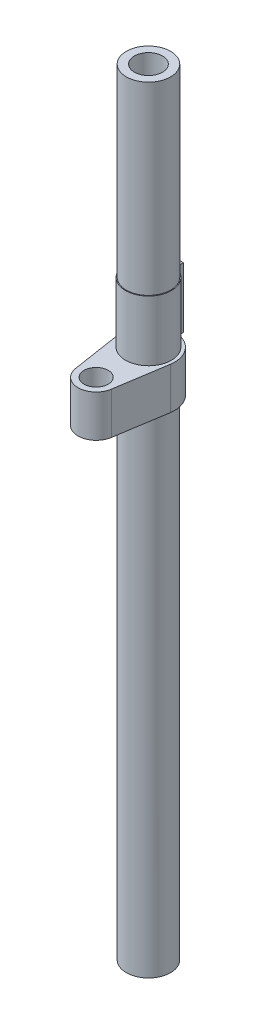
SolidWorks part; units mm, degrees
ref_plane "Ön Düzlem" through (0, 0, 0) normal (0, 0, 1) x (1, 0, 0)
ref_plane "Üst Düzlem" through (0, 0, 0) normal (0, 1, 0) x (1, 0, 0)
ref_plane "Sağ Düzlem" through (0, 0, 0) normal (1, 0, 0) x (0, 0, -1)
sketch "Sketch1" plane through (0, 0, 0) normal (0, 1, 0) x (1, 0, 0)
  circle A0 centre (0, 0) radius 2.75
  dimension "D1" = 5.5
extrude "Boss-Extrude1" add sketch "Sketch1" along normal blind 96.4
sketch "Sketch2" plane through (0, 0, 0) normal (0, -1, 0) x (1, 0, 0)
  circle A0 centre (0, 0) radius 1.75
  dimension "D1" = 3.5
extrude "Cut-Extrude1" cut sketch "Sketch2" against normal blind 8.9
extrude "Cut-Extrude2" cut sketch "Sketch2<2>" along normal blind 8.9 from surface starting at face at (0, 96.4, 2.75)
sketch "Sketch2<2>" plane through (0, 0, 0) normal (0, -1, 0) x (1, 0, 0) same geometry as "Sketch2"
ref_plane "Plane1" through (-2.75, 0, 0) normal (-1, 0, 0) x (0, 0, 1)
sketch "Sketch3" plane through (-2.75, 0, 0) normal (-1, 0, 0) x (0, 0, 1)
  line L0 (0, 6.15) -> (0, 0) construction
  line L1 (2.75, 96.4) -> (-2.75, 96.4) construction
  circle A0 centre (0, 6.15) radius 1.75
  circle A1 centre (0, 90.25) radius 1.75
  dimension "D2" = 3.5
  dimension "D1" = 6.15
  dimension "D3" = 6.15
extrude "Cut-Extrude3" cut sketch "Sketch3" against normal up to surface (2.75 mm away) up to face at (0, 87.5, 1.75)
ref_plane "Plane2" through (0, 73.45, 0) normal (0, 1, 0) x (1, 0, 0)
sketch "Sketch4" plane through (0, 73.45, 0) normal (0, 1, 0) x (1, 0, 0)
  line L0 (-0.75, 2.9047) -> (-0.75, 3.9047) construction
  line L1 (0.75, 2.9047) -> (0.75, 3.9047) construction
  line L2 (-0.75, 3.4047) -> (0.75, 3.4047) construction
  line L3 (-0.75, 3.9047) -> (0.75, 3.9047) construction
  line L4 (0.6, 2.7861) -> (0.6, 3.7547)
  line L5 (-0.6, 3.7547) -> (0.6, 3.7547)
  line L6 (-0.6, 2.7861) -> (-0.6, 3.7547)
  arc A0 (-0.75, 2.9047) -> (0.75, 2.9047) centre (0, 0) ccw construction
  arc A1 (-0.6, 2.7861) -> (0.6, 2.7861) centre (0, 0) ccw
  circle A2 centre (0, 0) radius 2.75 construction
  circle A3 centre (0, 0) radius 2.75
  point P9 (0, 3.4047)
  dimension "D1" = 6
  dimension "D2" = 1.5
  dimension "D3" = 1
  dimension "D4" = 0.15
extrude "Boss-Extrude2" add sketch "Sketch4" against normal blind 7.5
sketch "Sketch5" plane through (0, 65.95, 0) normal (0, -1, 0) x (1, 0, 0)
  line L0 (-3.2113, 0.5) -> (-2.2232, 6.8462)
  line L1 (2.2232, 6.8462) -> (3.2113, 0.5)
  arc A0 (2.2232, 6.8462) -> (-2.2232, 6.8462) centre (0, 6.5) ccw
  arc A1 (-3.2113, 0.5) -> (3.2113, 0.5) centre (0, 0) ccw
  circle A2 centre (0, 6.5) radius 1.5
  circle A3 centre (0, 0) radius 2.75 construction
  circle A4 centre (0, 0) radius 2.75
  dimension "D1" = 4.5
  dimension "D3" = 6.5
  dimension "D4" = 3
  dimension "D2" = 6.5
extrude "Boss-Extrude3" add sketch "Sketch5" along normal blind 5.2
